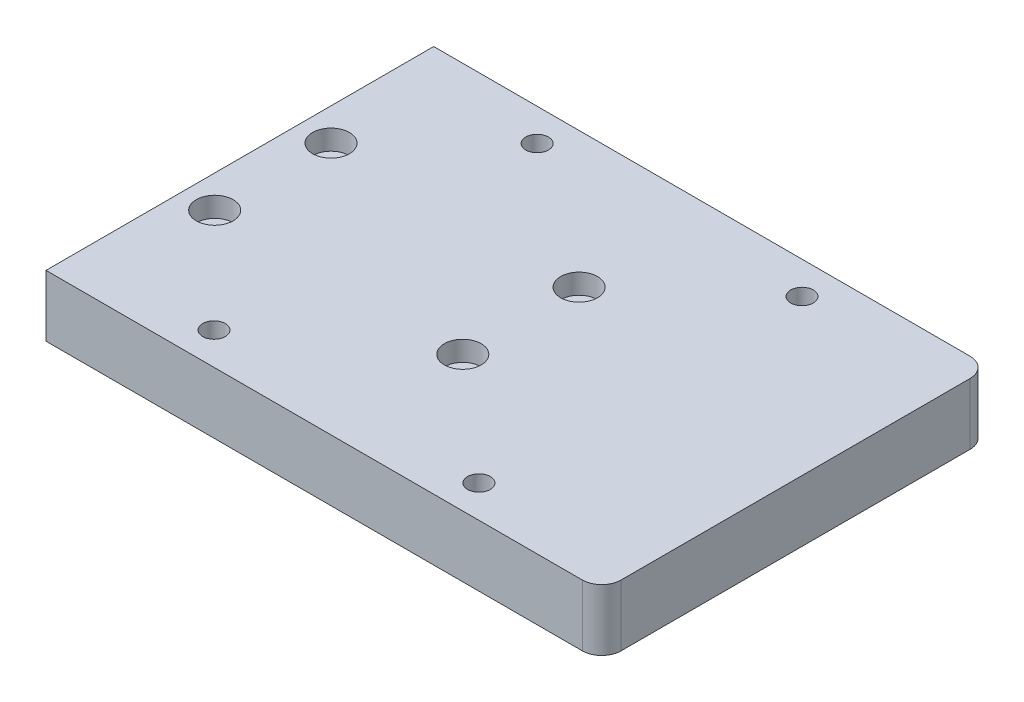
SolidWorks part; units mm, degrees
ref_plane "前视基准面" through (0, 0, 0) normal (0, 0, 1) x (1, 0, 0)
ref_plane "上视基准面" through (0, 0, 0) normal (0, 1, 0) x (1, 0, 0)
ref_plane "右视基准面" through (0, 0, 0) normal (1, 0, 0) x (0, 0, -1)
sketch "草图1" plane through (0, 0, 0) normal (0, 1, 0) x (1, 0, 0)
  line L1 (-43, 30) -> (43, 30)
  line L2 (-43, 30) -> (-43, -30)
  line L3 (-43, -30) -> (43, -30)
  line L4 (43, 30) -> (43, -30)
  line L5 (-43, 30) -> (43, -30) construction
  line L6 (-43, -30) -> (43, 30) construction
  point P0 (0, 0)
  dimension "D1" = 60
  dimension "D2" = 86
extrude "凸台-拉伸1" add sketch "草图1" along normal blind 9.5
fillet "圆角1" radius 3 2 edges at (43, 4.75, -30) (43, 4.75, 30)
sketch "草图2" plane through (0, 9.5, 0) normal (0, 1, 0) x (1, 0, 0)
  circle A0 centre (-38, -8.8898) radius 1.25
  circle A1 centre (-38, 9.1102) radius 1.25
  circle A2 centre (0.5, 9) radius 1.25
  circle A3 centre (0.5, -9) radius 1.25
  dimension "D1" = 2.5
extrude "切除-拉伸1" cut sketch "草图2" against normal through all
sketch "草图3" plane through (0, 9.5, 0) normal (0, 1, 0) x (1, 0, 0)
  circle A0 centre (-38, -8.8898) radius 2.85
  circle A1 centre (-38, 9.1102) radius 2.85
  circle A2 centre (0.5, -9) radius 2.85
  circle A3 centre (0.5, 9) radius 2.85
  dimension "D1" = 5.7
extrude "切除-拉伸2" cut sketch "草图3" against normal blind 3.1
sketch "草图4" plane through (0, 9.5, 0) normal (0, 1, 0) x (1, 0, 0)
  line L0 (-43, -30) -> (40, -30) construction
  line L1 (40, 30) -> (-43, 30) construction
  line L2 (43, -27) -> (43, 27) construction
  circle A0 centre (-22, -25) radius 1.75
  circle A1 centre (-22, 25) radius 1.75
  circle A2 centre (19, -25) radius 1.75
  circle A3 centre (19, 25) radius 1.75
  dimension "D1" = 3.5
  dimension "D2" = 5
  dimension "D3" = 5
  dimension "D4" = 5
  dimension "D5" = 5
  dimension "D6" = 24
  dimension "D7" = 24
  dimension "D8" = 65
  dimension "D9" = 65
extrude "切除-拉伸3" cut sketch "草图4" against normal through all
